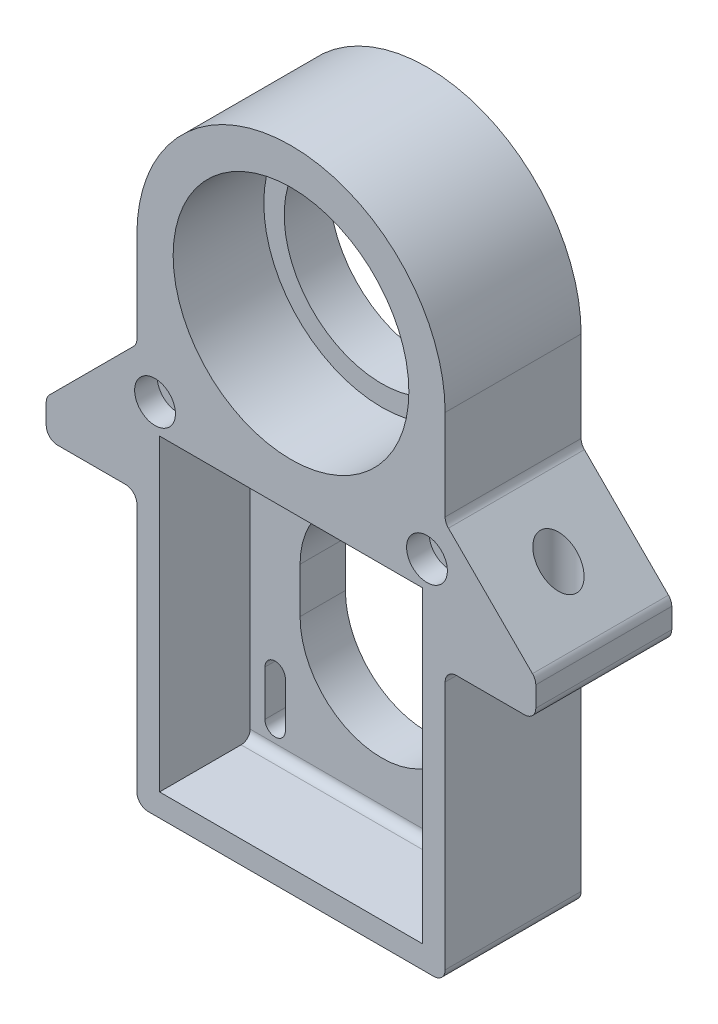
SolidWorks part; units mm, degrees
ref_plane "Plan de face" through (0, 0, 0) normal (0, 0, 1) x (1, 0, 0)
ref_plane "Plan de dessus" through (0, 0, 0) normal (0, 1, 0) x (1, 0, 0)
ref_plane "Plan de droite" through (0, 0, 0) normal (1, 0, 0) x (0, 0, -1)
sketch "Esquisse1" plane through (0, 0, 0) normal (0, 0, 1) x (1, 0, 0)
  line L0 (0, 0) -> (0, -75) construction
  line L1 (-34, 0) -> (-34, -41)
  line L2 (29, -104) -> (-29, -104)
  line L3 (29, -104) -> (29, -46)
  line L4 (29, -46) -> (-29, -46)
  line L5 (-29, -104) -> (-29, -46)
  line L6 (29, -104) -> (-29, -46) construction
  line L7 (29, -46) -> (-29, -104) construction
  line L8 (23.5, -98.5) -> (-23.5, -98.5)
  line L9 (23.5, -98.5) -> (23.5, -51.5)
  line L10 (23.5, -51.5) -> (-23.5, -51.5)
  line L11 (-23.5, -98.5) -> (-23.5, -51.5)
  line L12 (23.5, -98.5) -> (-23.5, -51.5) construction
  line L13 (23.5, -51.5) -> (-23.5, -98.5) construction
  line L14 (34, -109) -> (-34, -109)
  line L15 (34, -109) -> (34, -41)
  line L16 (34, -41) -> (-34, -41)
  line L17 (-34, -109) -> (-34, -41)
  line L18 (34, -109) -> (-34, -41) construction
  line L19 (34, -41) -> (-34, -109) construction
  line L20 (34, 0) -> (34, -41)
  line L21 (-34, -41) -> (34, -41)
  line L22 (26, 0) -> (34, -41)
  line L23 (-34, -41) -> (-54, -41)
  line L24 (-34, -41) -> (-34, -49)
  line L25 (-34, -49) -> (-54, -49)
  line L26 (-54, -41) -> (-54, -49)
  line L27 (34, -41) -> (54, -41)
  line L28 (34, -41) -> (34, -49)
  line L29 (34, -49) -> (54, -49)
  line L30 (54, -41) -> (54, -49)
  line L31 (-34, -41) -> (-26, 0)
  line L32 (-26, 0) -> (26, 0)
  line L33 (15, 0) -> (18, -75)
  line L34 (18, -75) -> (-18, -75)
  line L35 (-18, -75) -> (-15, 0)
  line L36 (30.5, 0) -> (18, -75)
  line L37 (-30.5, 0) -> (-18, -75)
  line L38 (-54, -41) -> (-34, -21)
  line L39 (54, -41) -> (34, -21)
  line L40 (23.5, -98.5) -> (23.5, -88.5) construction
  line L41 (21.25, -98.5) -> (21.25, -88.5)
  line L42 (25.75, -98.5) -> (25.75, -88.5)
  line L43 (23.5, -51.5) -> (23.5, -41.5) construction
  line L44 (21.25, -51.5) -> (21.25, -41.5)
  line L45 (25.75, -51.5) -> (25.75, -41.5)
  line L46 (-23.5, -51.5) -> (-23.5, -41.5) construction
  line L47 (-21.25, -51.5) -> (-21.25, -41.5)
  line L48 (-25.75, -51.5) -> (-25.75, -41.5)
  line L49 (-23.5, -98.5) -> (-23.5, -88.5) construction
  line L50 (-21.25, -98.5) -> (-21.25, -88.5)
  line L51 (-25.75, -98.5) -> (-25.75, -88.5)
  line L52 (0, -75) -> (0, -65) construction
  line L53 (-18, -75) -> (-18, -65)
  line L54 (18, -75) -> (18, -65)
  line L56 (29, -46) -> (-29, -46)
  line L57 (29, -46) -> (29, -36)
  line L58 (29, -36) -> (-29, -36)
  line L59 (-29, -46) -> (-29, -36)
  line L60 (34, -41) -> (-34, -41)
  line L61 (34, -41) -> (34, -31)
  line L62 (34, -31) -> (-34, -31)
  line L63 (-34, -41) -> (-34, -31)
  circle A0 centre (0, 0) radius 26
  circle A1 centre (0, 0) radius 34
  circle A2 centre (0, -75) radius 18
  circle A3 centre (0, 0) radius 21.5
  circle A4 centre (23.5, -51.5) radius 2.25
  circle A5 centre (23.5, -98.5) radius 2.25
  circle A6 centre (-23.5, -98.5) radius 2.25
  circle A7 centre (-23.5, -51.5) radius 2.25
  circle A8 centre (0, 0) radius 15
  circle A11 centre (0, 0) radius 30.5
  arc A14 (21.25, -98.5) -> (25.75, -98.5) centre (23.5, -98.5) ccw
  arc A15 (25.75, -88.5) -> (21.25, -88.5) centre (23.5, -88.5) ccw
  arc A16 (21.25, -51.5) -> (25.75, -51.5) centre (23.5, -51.5) ccw
  arc A17 (25.75, -41.5) -> (21.25, -41.5) centre (23.5, -41.5) ccw
  arc A18 (-21.25, -51.5) -> (-25.75, -51.5) centre (-23.5, -51.5) cw
  arc A19 (-25.75, -41.5) -> (-21.25, -41.5) centre (-23.5, -41.5) cw
  arc A20 (-21.25, -98.5) -> (-25.75, -98.5) centre (-23.5, -98.5) cw
  arc A21 (-25.75, -88.5) -> (-21.25, -88.5) centre (-23.5, -88.5) cw
  arc A22 (-18, -75) -> (18, -75) centre (0, -75) ccw
  arc A23 (18, -65) -> (-18, -65) centre (0, -65) ccw
  point P50 (23.5, -93.5)
  point P55 (23.5, -46.5)
  point P62 (-23.5, -46.5)
  point P68 (-23.5, -93.5)
  point P73 (0, -70)
  dimension "D1" = 52
  dimension "D2" = 68
  dimension "D5" = 36
  dimension "D8" = 20
  dimension "D12" = 43
  dimension "D13" = 4.5
  dimension "D14" = 30
  dimension "D18" = 61
  dimension "D3" = 29
  dimension "D4" = 47
  dimension "D6" = 75
  dimension "D7" = 34
  dimension "D9" = 20
  dimension "D10" = 8
  dimension "D11" = 8
  dimension "D19" = 45
  dimension "D20" = 45
  dimension "D21" = 10
  dimension "D22" = 10
  dimension "D23" = 34
  dimension "D24" = 10
  dimension "D25" = 10
extrude "Boss.-Extru.1" add sketch "Esquisse1" along normal blind 20 contours L23 L26 L25 L17 | L38 L23 L1 | L30 L27 L15 L29 | L27 L39 L20 | L5 L59 L16 L17 L14 L15 L57 L3 L2 | L31 L62 L1 | L37 L62 L31 L16 L59 L58 | L35 L62 L37 L58 | A1 L62 L35 L58 L33 | L36 L62 L33 L58 | L22 L62 L36 L58 L57 L16 | L20 L62 L22 | L31 L62 L37 A1 | A1 L37 L62 L35 | L31 A1 L1 L62 | A1 L35 L62 | A1 L62 L33 | A1 L33 L62 L36 | L22 A1 L36 L62 | L22 L62 L20 A1 | A11 L36 L22 A1 L31 L37 | A11 L37 L31 | A11 L31 L37 A1 L35 | L31 A1 L37 | A11 L35 A1 L62 L33 | L62 A1 | A11 L33 A1 L36 L22 | L36 A1 L22 | A11 L22 L36 | L37 A11 L31 A0 L22 L36 | L31 A11 L35 A0 | L35 A11 L33 A0 | L33 A11 L22 A0 | L37 A11 | L36 A11 region at (-32.3895, -19.4522, 0) region at (0, 33.149, 0) region at (-40.6667, -34.3333, 0) region at (32.3895, -19.4522, 0) region at (-28.6445, -25.8495, 0) region at (-28.2814, -16.7754, 0) region at (-33.3496, -34.3333, 0) region at (-44, -45, 0) region at (40.6667, -34.3333, 0) region at (28.2814, -16.7754, 0) region at (28.6445, -25.8495, 0) region at (-29.6715, -35.4552, 0) region at (-28.5064, -11.2991, 0) region at (-22.5014, -22.3906, 0) region at (-22.6384, -27.7985, 0) region at (-31.5, -41.9617, 0) region at (33.3496, -34.3333, 0) region at (44, -45, 0) region at (22.5014, -22.3906, 0) region at (28.5064, -11.2991, 0) region at (29.6715, -35.4552, 0) region at (22.6384, -27.7985, 0) region at (-20.6315, -33.4498, 0) region at (-28.4905, -10.6784, 0) region at (-22.651, -15.5477, 0) region at (-29.8395, -4.9733, 0) region at (-15.4786, -30.637, 0) region at (-15.7892, -27.932, 0) region at (22.651, -15.5477, 0) region at (29.8395, -4.9733, 0) region at (20.6315, -33.4498, 0) region at (15.4786, -30.637, 0) region at (0, -34.19, 0) region at (0, -26.5816, 0) region at (0, -32.2047, 0)
extrude "Boss.-Extru.2" add sketch "Esquisse1<4>" against normal blind 10 contours A11 L36 L22 A1 L31 L37 | L37 A11 L31 A0 L22 L36 | A3 L32 A0 | A3 L32 A0 L35 | A3 L35 A0 L33 | A3 L33 A0 L32 | L31 A11 L35 A0 | L35 A11 L33 A0 | L33 A11 L22 A0 | A11 L33 A1 L36 L22 | L36 A1 L22 | L22 L62 L20 A1 | L22 A1 L36 L62 | A1 L33 L62 L36 | L27 L39 L20 | A11 L35 A1 L62 L33 | A1 L35 L62 | A1 L37 L62 L35 | A11 L31 L37 A1 L35 | L31 L62 L37 A1 | L31 A1 L1 L62 | L31 A1 L37 | A11 L37 L31 | L37 A11 | A11 L22 L36 | L36 A11 | L35 L4 L33 L21 | L16 A19 L47 L4 L35 | A17 L60 L33 L4 L44 | A17 L45 L4 L57 L21 | L5 L59 L16 L17 L14 L15 L57 L3 L2 | L30 L27 L15 L29 | A23 L10 L33 L4 L35 | L10 L44 L4 L33 | L51 A21 L11 A7 L48 L4 L5 L2 L3 L45 A4 L9 A15 L42 A5 L8 A6 | L47 L10 L35 L4 | L48 A19 L60 L59 L4 | A23 L10 L35 | A23 L35 L10 A7 L37 L53 | L11 A21 L50 L8 L41 A15 L9 A4 L36 A2 L37 A7 | A23 L54 L36 A4 L10 L33 | A23 L33 L10 | L20 L62 L22 | A1 L62 L33 | L38 L23 L1 | L23 L26 L25 L17 | L33 L58 L35 L21 | L36 L62 L33 L58 | L37 A19 L16 L35 L58 | L60 A19 L37 L58 L59 | L37 L62 L31 L16 L59 L58 | L35 L62 L37 L58 | A1 L62 L35 L58 L33 | L62 A1 | L31 L62 L1 | A17 L21 L57 L58 L36 | A17 L36 L58 L33 L60 | L22 L62 L36 L58 L57 L16 region at (-32.3895, -19.4522, 0) region at (0, 33.149, 0) region at (-40.6667, -34.3333, 0) region at (32.3895, -19.4522, 0) region at (-28.6445, -25.8495, 0) region at (-28.2814, -16.7754, 0) region at (-33.3496, -34.3333, 0) region at (-44, -45, 0) region at (40.6667, -34.3333, 0) region at (28.2814, -16.7754, 0) region at (28.6445, -25.8495, 0) region at (-29.6715, -35.4552, 0) region at (-28.5064, -11.2991, 0) region at (-22.5014, -22.3906, 0) region at (-22.6384, -27.7985, 0) region at (-31.5, -41.9617, 0) region at (33.3496, -34.3333, 0) region at (44, -45, 0) region at (22.5014, -22.3906, 0) region at (28.5064, -11.2991, 0) region at (29.6715, -35.4552, 0) region at (22.6384, -27.7985, 0) region at (-20.6315, -33.4498, 0) region at (-28.4905, -10.6784, 0) region at (-22.651, -15.5477, 0) region at (-29.8395, -4.9733, 0) region at (-15.4786, -30.637, 0) region at (-15.7892, -27.932, 0) region at (-26.7416, -38.3869, 0) region at (-27.3741, -43.4986, 0) region at (22.651, -15.5477, 0) region at (29.8395, -4.9733, 0) region at (20.6315, -33.4498, 0) region at (15.4786, -30.637, 0) region at (-20.0715, -38.2662, 0) region at (0, -34.19, 0) region at (0, 25.4186, 0) region at (-21.0973, -9.5699, 0) region at (0, -26.5816, 0) region at (0, -32.2047, 0) region at (-27.375, -46.8202, 0) region at (27.3741, -43.4986, 0) region at (26.7416, -38.3869, 0) region at (21.0973, -9.5699, 0) region at (20.0715, -38.2662, 0) region at (0, -38.505, 0) region at (0, -21.7134, 0) region at (-18.9956, -43.4805, 0) region at (0, -43.505, 0) region at (18.9956, -43.4805, 0) region at (-19.0995, -48.7266, 0) region at (0, -46.3456, 0) region at (-22.1942, -54.0953, 0) region at (19.0995, -48.7266, 0) region at (-19.0403, -58.9719, 0) region at (-15.6289, -54.0682, 0) region at (15.6289, -54.0682, 0) region at (19.0403, -58.9719, 0)
sketch "Esquisse1<4>" plane through (0, 0, 0) normal (0, 0, 1) x (1, 0, 0) same geometry as "Esquisse1"
sketch "Esquisse2" plane through (0, -49, 0) normal (0, -1, 0) x (1, 0, 0)
  line L0 (0, 20) -> (0, -10) construction
  line L2 (34, -10) -> (-34, -10) construction
  line L3 (54, 5) -> (-54, 5) construction
  line L4 (54, 20) -> (54, -10) construction
  line L5 (-54, 20) -> (-54, -10) construction
  line L6 (34, 20) -> (-34, 20) construction
  circle A3 centre (44, 5) radius 4
  circle A5 centre (-44, 5) radius 4
  dimension "D1" = 8
  dimension "D2" = 0
  dimension "D3" = 10
extrude "Enlèv. mat.-Extru.2" cut sketch "Esquisse2" against normal through all
fillet "Congé1" radius 2.5 10 edges at (34, -21, 5) (-34, -21, 5) (-54, -41, 5) (54, -49, 5) (54, -41, 5) (-54, -49, 5) (-34, -49, 5) (-34, -109, 5) (34, -109, 5) (34, -49, 5)
sketch "Esquisse3" plane through (0, 0, 20) normal (0, 0, 1) x (1, 0, 0)
  line L0 (0, 0) -> (0, -61.2868) construction
  circle A0 centre (-30, -30) radius 2.5
  circle A1 centre (30, -30) radius 2.5
  circle A2 centre (-30, -30) radius 4.5
  circle A3 centre (30, -30) radius 4.5
  dimension "D3" = 5
  dimension "D4" = 9
  dimension "D1" = 30
  dimension "D2" = 30
extrude "Enlèv. mat.-Extru.3" cut sketch "Esquisse3" against normal through all contours A0 | A1 region at (-30, -30, 20) region at (30, -30, 20)
extrude "Enlèv. mat.-Extru.4" cut sketch "Esquisse3<3>" against normal blind 5
sketch "Esquisse3<3>" plane through (0, 0, 20) normal (0, 0, 1) x (1, 0, 0) same geometry as "Esquisse3"
fillet "Congé3" radius 2 2 edges at (0, -104, 0) (0, -36, 0)
